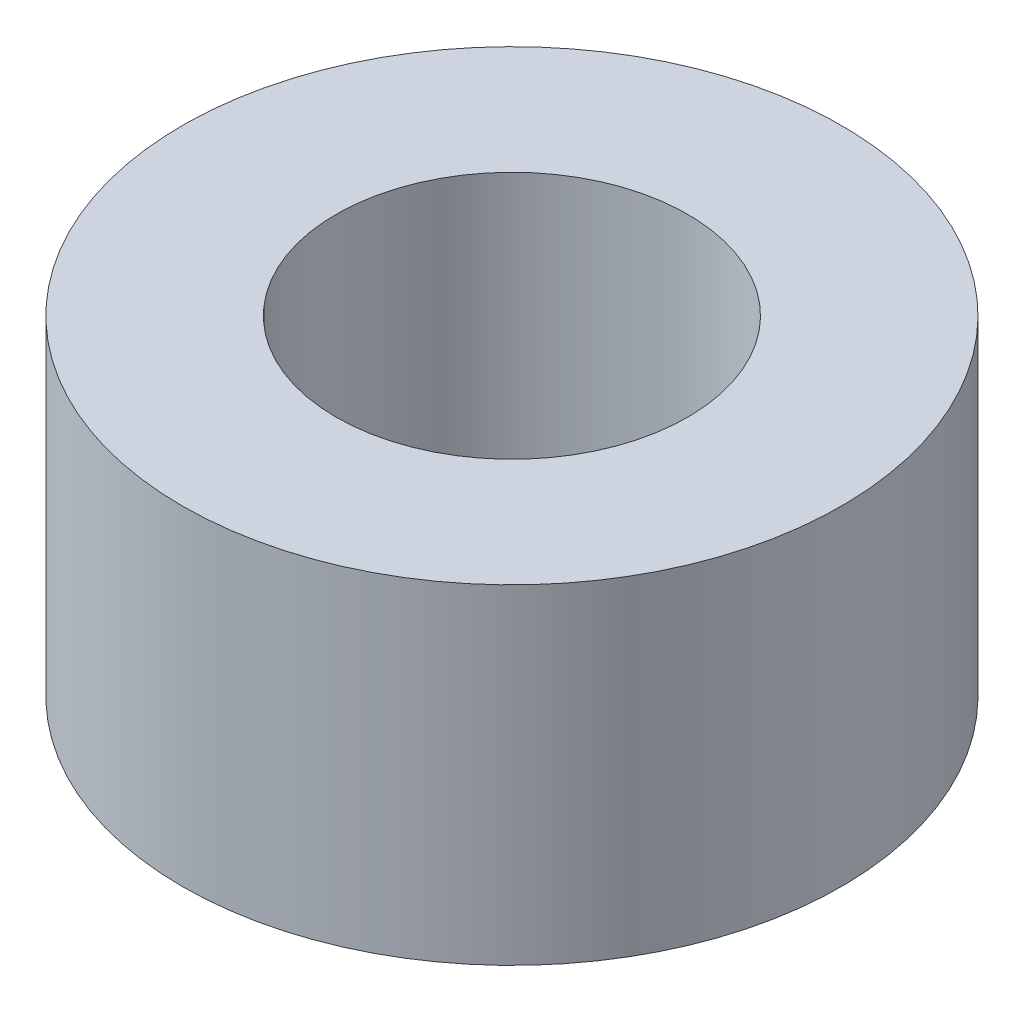
SolidWorks part; units mm, degrees
ref_plane "Front Plane" through (0, 0, 0) normal (0, 0, 1) x (1, 0, 0)
ref_plane "Top Plane" through (0, 0, 0) normal (0, 1, 0) x (1, 0, 0)
ref_plane "Right Plane" through (0, 0, 0) normal (1, 0, 0) x (0, 0, -1)
sketch "Sketch1" plane through (0, 0, 0) normal (0, 1, 0) x (1, 0, 0)
  circle A1 centre (0, 0) radius 1.6
  circle A3 centre (0, 0) radius 3
  dimension "D2" = 3.2
  dimension "D4" = 6
extrude "Boss-Extrude1" add sketch "Sketch1" along normal blind 3 contours A1 | A3 region at (0, 0, 0)
